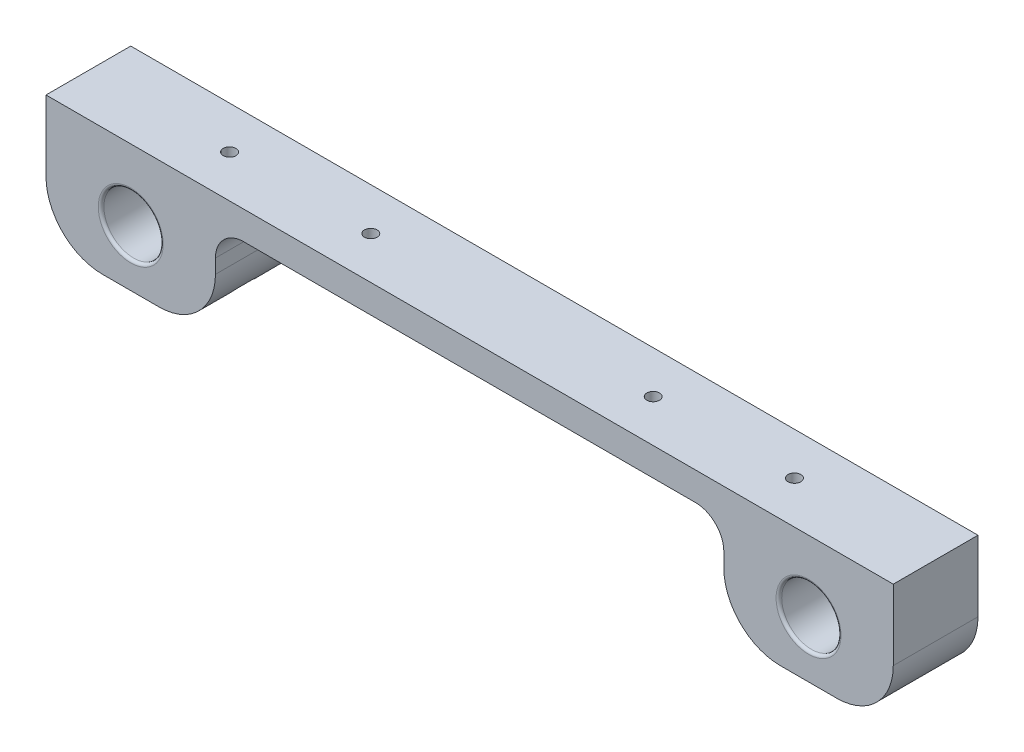
SolidWorks part; units mm, degrees
ref_plane "Front Plane" through (0, 0, 0) normal (0, 0, 1) x (1, 0, 0)
ref_plane "Top Plane" through (0, 0, 0) normal (0, 1, 0) x (1, 0, 0)
ref_plane "Right Plane" through (0, 0, 0) normal (1, 0, 0) x (0, 0, -1)
sketch "Sketch1" plane through (0, 0, 0) normal (0, 0, 1) x (1, 0, 0)
  line L1 (0, 0) -> (300, 0)
  line L2 (0, 0) -> (0, 45)
  line L3 (0, 45) -> (300, 45)
  line L4 (300, 0) -> (300, 45)
  dimension "D1" = 300
  dimension "D2" = 45
extrude "Boss-Extrude1" add sketch "Sketch1" along normal blind 30
sketch "Sketch2" plane through (0, 0, 30) normal (0, 0, 1) x (1, 0, 0)
  line L0 (7.9767, 20) -> (307.9767, 20) construction
  line L1 (0, 45) -> (0, 0) construction
  line L2 (150, 0) -> (150, 40) construction
  line L4 (300, 45) -> (0, 45) construction
  line L5 (0, 0) -> (300, 0) construction
  circle A0 centre (30, 20) radius 10.5
  circle A1 centre (270, 20) radius 10.5
  dimension "D1" = 30
  dimension "D2" = 21
  dimension "D4" = 9.5
  dimension "25" = 25
extrude "Cut-Extrude1" cut sketch "Sketch2" against normal through all
sketch "Sketch3" plane through (0, 0, 0) normal (0, -1, 0) x (1, 0, 0)
  line L0 (150, 0) -> (150, 30) construction
  line L1 (0, 30) -> (300, 30) construction
  line L2 (60, 30) -> (240, 30)
  line L3 (60, 30) -> (60, 0)
  line L4 (60, 0) -> (240, 0)
  line L5 (240, 30) -> (240, 0)
  line L6 (0, 0) -> (300, 0) construction
  dimension "D1" = 90
  dimension "D2" = 90
extrude "Cut-Extrude2" cut sketch "Sketch3" against normal blind 35
fillet "Fillet1" radius 20 1 edges at (0, 0, 15) type face fillet first side face at (0, 22.5, 15) second side face at (30, 0, 15)
fillet "Fillet2" radius 20 1 edges at (60, 0, 15) type face fillet first side face at (60, 17.5, 15) second side face at (40, 0, 15)
fillet "Fillet3" radius 20 1 edges at (240, 0, 15) type face fillet first side face at (240, 17.5, 15) second side face at (270, 0, 15)
fillet "Fillet4" radius 20 1 edges at (300, 0, 15) type face fillet first side face at (300, 22.5, 15) second side face at (280, 0, 15)
fillet "Fillet5" radius 10 1 edges at (240, 35, 15) type face fillet first side face at (240, 27.5, 15) second side face at (150, 35, 15)
fillet "Fillet6" radius 10 1 edges at (60, 35, 15) type face fillet first side face at (145, 35, 15) second side face at (60, 27.5, 15)
sketch "Sketch4" plane through (0, 45, 0) normal (0, 1, 0) x (1, 0, 0)
  line L0 (300, 0) -> (0, 0) construction
  line L1 (0, -30) -> (0, 0) construction
  circle A0 centre (50, -15) radius 2.25
  circle A1 centre (100, -15) radius 2.25
  circle A3 centre (200, -15) radius 2.25
  circle A4 centre (250, -15) radius 2.25
  circle A5 centre (150, -15) radius 2.25 [skipped]
  point P9 (0, -15)
  dimension "D1" = 15
  dimension "D2" = 50
  dimension "D3" = 4.5
  dimension "D4" = 5
extrude "Cut-Extrude3" cut sketch "Sketch4" against normal through all
sketch "Sketch5" plane through (0, 35, 0) normal (0, -1, 0) x (1, 0, 0)
  circle A0 centre (50, 15) radius 5
  circle A1 centre (250, 15) radius 5
  dimension "D1" = 10
  dimension "D2" = 10
extrude "Cut-Extrude4" cut sketch "Sketch5" against normal blind 7 from surface starting at face at (270, 0, 15)
fillet "Fillet7" radius 1 2 edges at (250.884, 2.1984, 19.9212) (50.8444, 3.1953, 19.9282)
chamfer "Chamfer1" distance 0.5 angle 45 4 edges at (250, 7, 17.25) (200, 35, 12.75) (100, 35, 12.75) (50, 7, 17.25)
fillet "Fillet8" radius 1 4 edges at (40.5, 20, 30) (40.5, 20, 0) (259.5, 20, 30) (259.5, 20, 0)
